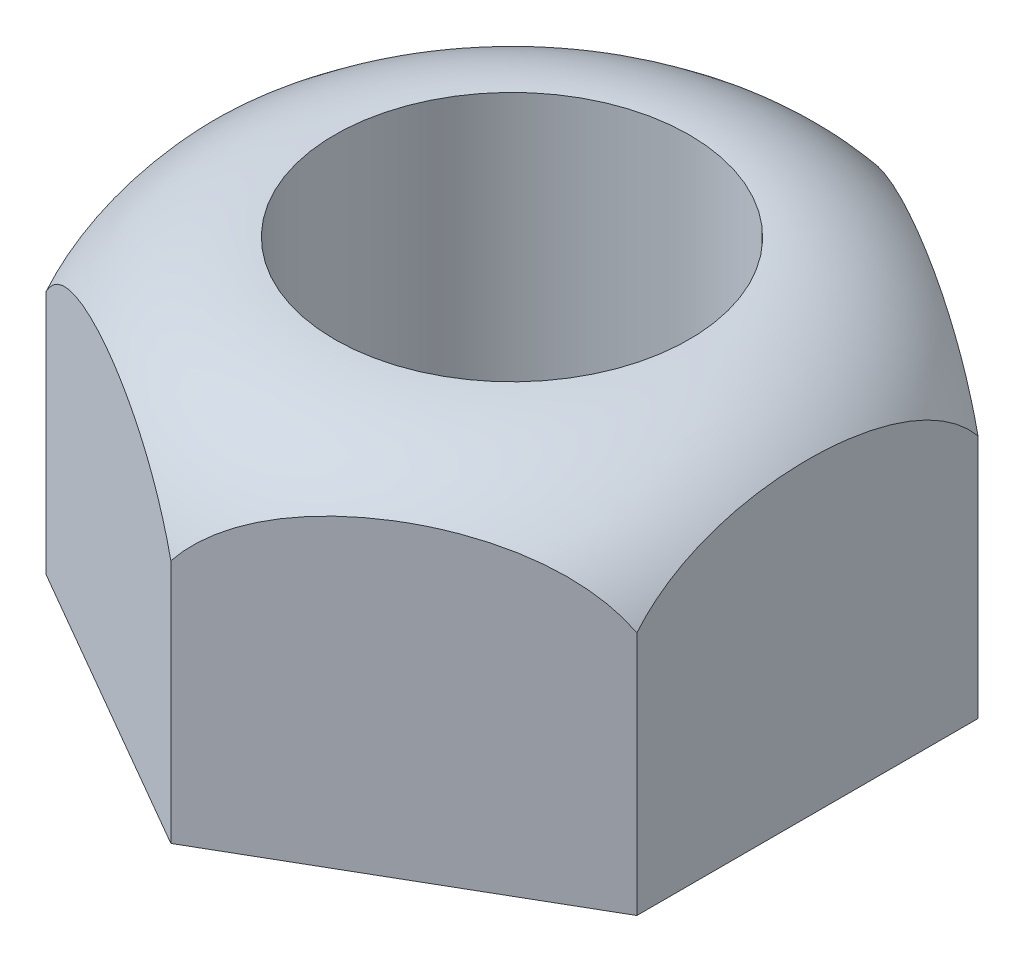
SolidWorks part; units mm, degrees
material "Alloy Steel"
ref_plane "Front Plane" through (0, 0, 0) normal (0, 0, 1) x (1, 0, 0)
ref_plane "Top Plane" through (0, 0, 0) normal (0, 1, 0) x (1, 0, 0)
ref_plane "Right Plane" through (0, 0, 0) normal (1, 0, 0) x (0, 0, -1)
sketch "Sketch1" plane through (0, 0, 0) normal (0, 1, 0) x (1, 0, 0)
  line L0 (0, 3) -> (0, 2) construction
  line L1 (0, 5.7735) -> (-5, 2.8868) construction
  line L2 (-5, 2.8868) -> (-5, -2.8868) construction
  line L3 (-5, -2.8868) -> (0, -5.7735) construction
  line L4 (0, -5.7735) -> (5, -2.8868) construction
  line L5 (5, -2.8868) -> (5, 2.8868) construction
  line L6 (5, 2.8868) -> (0, 5.7735) construction
  circle A0 centre (0, 0) radius 5 construction
  circle A1 centre (0, 0) radius 3 construction
  point P12 (0, -3)
  dimension "Thread Size" = 6
  dimension "Width" = 10
  dimension "Thread Pitch" = 1
sketch "Sketch2" plane through (0, 0, 0) normal (0, 0, 1) x (1, 0, 0)
  line L0 (0, -3) -> (0, 3) construction
  point P4 (0, 0)
  dimension "Height" = 6
sketch "Sketch3" plane through (0, 0, 0) normal (0, 1, 0) x (1, 0, 0)
  line L0 (5, 2.8868) -> (0, 5.7735) construction
  line L1 (5, -2.8868) -> (5, 2.8868) construction
  line L2 (0, -5.7735) -> (5, -2.8868) construction
  line L3 (-5, -2.8868) -> (0, -5.7735) construction
  line L4 (-5, 2.8868) -> (-5, -2.8868) construction
  line L5 (0, 5.7735) -> (-5, 2.8868) construction
  line L6 (5, 2.8868) -> (0, 5.7735)
  line L7 (5, -2.8868) -> (5, 2.8868)
  line L8 (0, -5.7735) -> (5, -2.8868)
  line L9 (-5, -2.8868) -> (0, -5.7735)
  line L10 (-5, 2.8868) -> (-5, -2.8868)
  line L11 (0, 5.7735) -> (-5, 2.8868)
  circle A0 centre (0, 0) radius 3 construction
  circle A1 centre (0, 0) radius 3
extrude "Boss-Extrude1" add sketch "Sketch3" along normal mid plane 6
ref_plane "Plane1" through (0, 3, 0) normal (0, 1, 0) x (1, 0, 0)
sketch "Sketch5" plane through (0, 0, 0) normal (1, 0, 0) x (0, 0, -1)
  line L0 (5.7735, 3) -> (5.7735, -3) construction
  line L1 (2.8868, 3) -> (5.7735, 3) construction
  line L3 (3, 3) -> (5.7735, 3)
  line L4 (5.7735, 3) -> (5.7735, 1.1435)
  line L5 (0, 0) -> (0, 1.85) construction
  line L6 (0, -3) -> (0, 3) construction
  arc A0 (3, 3) -> (5.7735, 1.1435) centre (3, 0) cw
  dimension "D1" = 3
revolve "Cut-Revolve1" cut sketch "Sketch5" angle 360 about L5
sketch "Ref" plane through (0, 0, 0) normal (0, 0, 1) x (1, 0, 0)
  line L0 (-5, -3) -> (-5, 3) construction
  dimension "D1" = 6
sketch "Sketch7" [suppressed] plane through (0, 3, 0) normal (0, 1, 0) x (1, 0, 0)
  circle A0 centre (0, 0) radius 3 construction
  circle A1 centre (0, 0) radius 3
curve "Helix/Spiral1" [suppressed] pitch 1 height 7 turns 7
sketch "Sketch8" [suppressed] plane through (0, 0, 0) normal (0, 0, 1) x (1, 0, 0)
  line L0 (-3, 3.875) -> (-3, 3)
  line L1 (-3, 3) -> (-2.3505, 3.375)
  line L2 (-2.3505, 3.5) -> (-3, 3.875)
  line L3 (-2.3505, 3.5) -> (-2.3505, 3.375)
  line L4 (-2.3505, 3.4375) -> (-3, 3.4375) construction
  line L5 (-2.6752, 3.1875) -> (-2.6752, 3.6875) construction
  point P11 (-2.6752, 3.4375)
  dimension "D1" = 60
  dimension "D2" = 0.125
  dimension "D3" = 0.5
sweep "Sweep1" [suppressed] add profiles "Sketch8" path "Helix/Spiral1"
sketch "Sketch9" [suppressed] plane through (0, 3, 0) normal (0, 1, 0) x (1, 0, 0)
  circle A1 centre (0, 0) radius 3
  circle A2 centre (0, 0) radius 3
  dimension "D1" = 0
extrude "Cut-Extrude2" [suppressed] cut sketch "Sketch9" along normal through all
mirror "Mirror1" [suppressed] about plane through (0, 0, 0) normal (0, 1, 0)
sketch "Sketch10" [suppressed] plane through (0, 3, 0) normal (0, 1, 0) x (1, 0, 0)
  circle A0 centre (0, 0) radius 3.1
  circle A2 centre (0, 0) radius 3 construction
  dimension "D2" = 6
extrude "Cut-Extrude3" [suppressed] cut sketch "Sketch10" against normal through all draft 45
equation "\"D1@Boss-Extrude1\"=\"Height@Sketch2\""
equation "\"D1@Sketch5\"=(\"Height@Sketch2\"*.5)"
equation "\"D4@Helix/Spiral1\"=\"Thread Pitch@Sketch1\""
equation "\"D3@Helix/Spiral1\"=\"Height@Sketch2\"+\"Thread Pitch@Sketch1\""
equation "\"D2@Sketch8\"=\"Thread Pitch@Sketch1\"*.125"
equation "\"D3@Sketch8\"=\"Thread Pitch@Sketch1\"*.5"
equation "\"D3@Cut-Extrude3\"=\"Thread Pitch@Sketch1\"*.75"
equation "\"D1@Sketch10\"=\"Thread Pitch@Sketch1\"*.1"
equation "\"D2@Sketch10\"=\"Thread Size@Sketch1\""
equation "\"D1@Ref\"=\"Height@Sketch2\""
